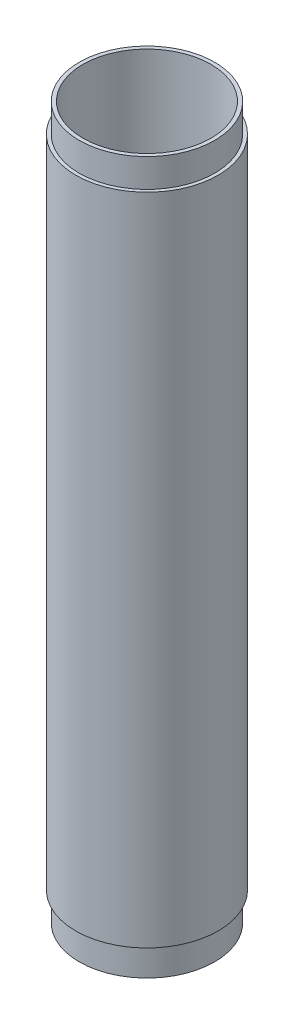
SolidWorks part; units mm, degrees
ref_plane "Спереди" through (0, 0, 0) normal (0, 0, 1) x (1, 0, 0)
ref_plane "Сверху" through (0, 0, 0) normal (0, 1, 0) x (1, 0, 0)
ref_plane "Справа" through (0, 0, 0) normal (1, 0, 0) x (0, 0, -1)
sketch "Эскиз1" plane through (0, 0, 0) normal (0, 1, 0) x (1, 0, 0)
  circle A0 centre (0, 0) radius 25
  circle A1 centre (0, 0) radius 22.5
  dimension "D1" = 50
  dimension "D2" = 45
extrude "Бобышка-Вытянуть1" add sketch "Эскиз1" along normal blind 230
sketch "Эскиз2" plane through (0, 0, 0) normal (0, 1, 0) x (1, 0, 0)
  circle A0 centre (0, 0) radius 24
  dimension "D1" = 48
extrude "Вырез-Вытянуть1" cut sketch "Эскиз2" along normal blind 20
sketch "Эскиз4" plane through (0, 230, 0) normal (0, 1, 0) x (1, 0, 0)
  circle A0 centre (0, 0) radius 23.8
  circle A6 centre (0, 0) radius 22.5
  dimension "D1" = 47.6
  dimension "D2" = 45
extrude "Бобышка-Вытянуть2" add sketch "Эскиз4" along normal blind 10
sketch "Эскиз6" plane through (0, 20, 0) normal (0, -1, 0) x (1, 0, 0)
  circle A0 centre (0, 0) radius 22.5
  circle A1 centre (0, 0) radius 24
  dimension "D1" = 45
  dimension "D2" = 48
extrude "Бобышка-Вытянуть3" add sketch "Эскиз6" along normal blind 20
sketch "Эскиз7" plane through (0, 0, 0) normal (0, -1, 0) x (1, 0, 0)
  circle A0 centre (0, 0) radius 22.5
  circle A1 centre (0, 0) radius 23.8
  dimension "D1" = 45
  dimension "D2" = 47.6
extrude "Бобышка-Вытянуть4" add sketch "Эскиз7" along normal blind 10
